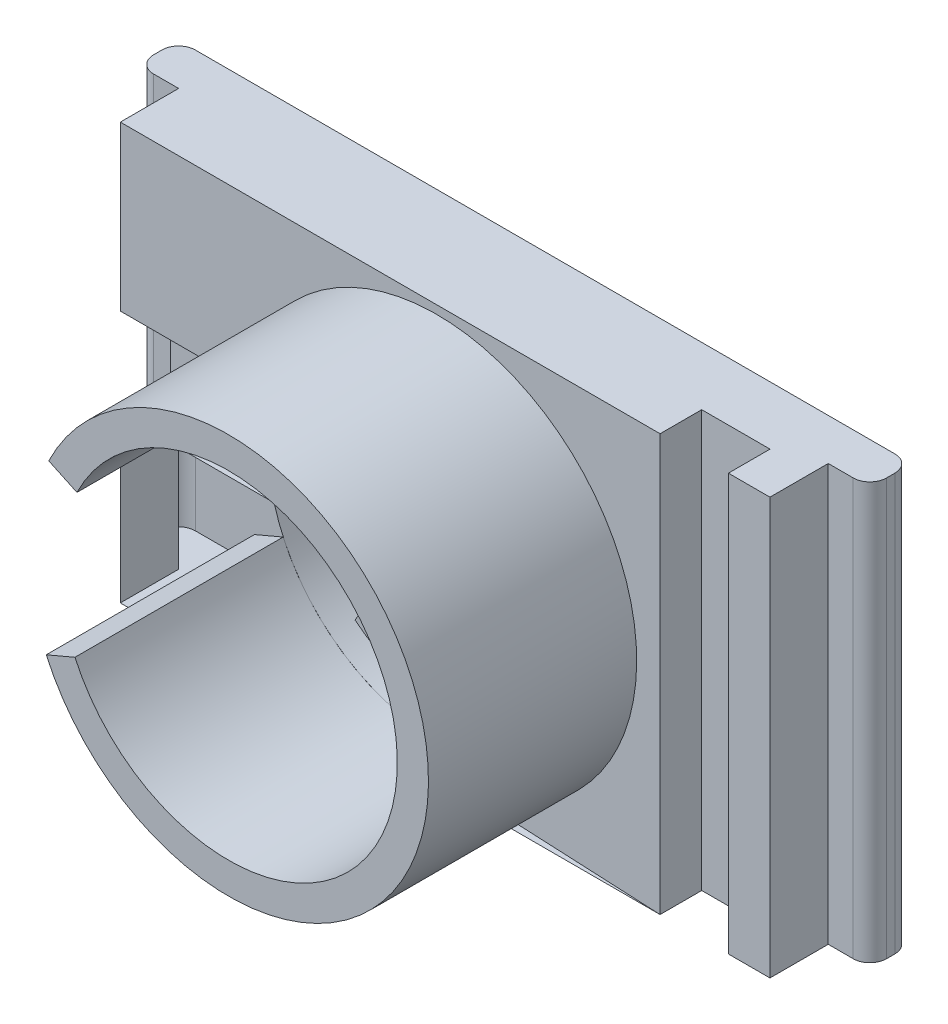
SolidWorks part; units mm, degrees
ref_plane "Front Plane" through (0, 0, 0) normal (0, 0, 1) x (1, 0, 0)
ref_plane "Top Plane" through (0, 0, 0) normal (0, 1, 0) x (1, 0, 0)
ref_plane "Right Plane" through (0, 0, 0) normal (1, 0, 0) x (0, 0, -1)
sketch "Sketch1" plane through (0, 0, 0) normal (0, 0, 1) x (1, 0, 0)
  line L1 (-32.5, -25) -> (32.5, -25)
  line L2 (-32.5, -25) -> (-32.5, 25)
  line L3 (-32.5, 25) -> (32.5, 25)
  line L4 (32.5, -25) -> (32.5, 25)
  line L5 (-32.5, -25) -> (32.5, 25) construction
  line L6 (-32.5, 25) -> (32.5, -25) construction
  point P0 (0, 0)
  dimension "D1" = 0
  dimension "D2" = 50
  dimension "D3" = 65
extrude "Boss-Extrude1" add sketch "Sketch1" along normal blind 12
sketch "Sketch2" plane through (0, 0, 12) normal (0, 0, 1) x (1, 0, 0)
  line L0 (32.5, -25) -> (32.5, 25) construction
  line L1 (-32.5, -25) -> (32.5, -25) construction
  line L2 (-1.6792, -18.9347) -> (-0.0792, -16.1634)
  line L3 (-44.0305, 5.35) -> (-14.0305, 5.35)
  line L4 (-44.0305, 5.35) -> (-44.0305, -5.35)
  line L5 (-44.0305, -5.35) -> (-14.0305, -5.35)
  line L6 (-14.0305, 5.35) -> (-14.0305, -5.35)
  line L7 (-7.3083, -15.6847) -> (-5.7083, -12.9134)
  line L8 (25.4875, 3.25) -> (22.2875, 3.25)
  line L9 (25.4875, 3.25) -> (25.4875, -3.25)
  line L10 (25.4875, -3.25) -> (22.2875, -3.25)
  line L11 (22.2875, 3.25) -> (22.2875, -3.25)
  line L12 (-0.0792, -16.1634) -> (-5.7083, -12.9134)
  line L13 (-7.3083, 15.6847) -> (-5.7083, 12.9134)
  line L14 (-1.6792, 18.9347) -> (-0.0792, 16.1634)
  line L15 (-5.7083, 12.9134) -> (-0.0792, 16.1634)
  line L16 (5.5, 0) -> (22.2875, -3.25) construction
  circle A0 centre (5.5, 0) radius 20.25
  point P25 (8, -1.4434)
  dimension "D1" = 20.25
  dimension "DK" = 40.5
  dimension "D2" = 27
  dimension "D3" = 25
  dimension "D4" = 20.25
  dimension "D5" = 30
  dimension "D6" = 10.7
  dimension "D7" = 20.25
  dimension "D8" = 20.25
  dimension "D9" = 6.5
  dimension "D10" = 3.2
  dimension "D11" = 3
  dimension "D12" = 17.0992
extrude "Cut-Extrude1" cut sketch "Sketch2" against normal blind 6 contours A0 L6 L10 L11 L8 | A0 L3 L4 L5 | L6 A0 region at (5.5839, 0, 12) region at (-14.3187, 0, 12) region at (-29.2704, 0, 12)
sketch "Sketch3" plane through (0, 0, 6) normal (0, 0, 1) x (1, 0, 0)
  circle A0 centre (5.5, 0) radius 9
  arc A1 (-1.6792, -18.9347) -> (25.4875, -3.25) centre (5.5, 0) ccw construction
  dimension "D2" = 18
  dimension "D1" = 0
extrude "Cut-Extrude2" cut sketch "Sketch3" against normal through all
sketch "Sketch4" plane through (0, 0, 12) normal (0, 0, 1) x (1, 0, 0)
  circle A0 centre (5.5, 0) radius 20.25
  arc A1 (-1.6792, -18.9347) -> (25.4875, -3.25) centre (5.5, 0) ccw construction
  dimension "D2" = 0
  dimension "D1" = 0
extrude "Cut-Extrude3" cut sketch "Sketch4" against normal blind 3
sketch "Sketch5" plane through (32.5, 0, 0) normal (1, 0, 0) x (0, 0, -1)
  line L0 (-12, -25) -> (-12, 25) construction
  line L1 (-12, -25) -> (0, -25)
  line L2 (-12, -25) -> (-12, 25)
  line L3 (-12, 25) -> (0, 25)
  line L4 (0, -25) -> (0, 25)
  line L5 (0, -25) -> (0, 25) construction
  line L6 (-12, 25) -> (0, 25) construction
  line L7 (-12, -25) -> (0, -25) construction
  dimension "D1" = 0
  dimension "D2" = 0
  dimension "D3" = 0
  dimension "D4" = 0
extrude "Boss-Extrude2" add sketch "Sketch5" along normal blind 13
sketch "Sketch6" plane through (0, 0, 12) normal (0, 0, 1) x (1, 0, 0)
  line L0 (-32.5, -25) -> (45.5, -25) construction
  line L1 (40.509, -25) -> (32.309, -25)
  line L2 (40.509, -25) -> (40.509, 25)
  line L3 (40.509, 25) -> (32.309, 25)
  line L4 (32.309, -25) -> (32.309, 25)
  line L5 (45.5, 25) -> (-32.5, 25) construction
  dimension "D1" = 0
  dimension "D2" = 8.2
  dimension "D3" = 0
extrude "Cut-Extrude4" cut sketch "Sketch6" against normal blind 5
sketch "Sketch7" plane through (45.5, 0, 0) normal (1, 0, 0) x (0, 0, -1)
  line L0 (-12, -25) -> (0, -25) construction
  line L1 (-5, -25) -> (0, -25)
  line L2 (-5, -25) -> (-5, 25)
  line L3 (-5, 25) -> (0, 25)
  line L4 (0, -25) -> (0, 25)
  line L5 (0, -25) -> (0, 25) construction
  line L6 (0, 25) -> (-12, 25) construction
  dimension "D1" = 0
  dimension "D2" = 0
  dimension "D3" = 0
  dimension "D4" = 5
extrude "Boss-Extrude3" add sketch "Sketch7" along normal blind 5
sketch "Sketch8" plane through (-32.5, 0, 0) normal (-1, 0, 0) x (0, 0, 1)
  line L0 (12, 25) -> (0, 25) construction
  line L1 (5, 25) -> (0, 25)
  line L2 (5, 25) -> (5, -25)
  line L3 (5, -25) -> (0, -25)
  line L4 (0, 25) -> (0, -25)
  line L5 (12, -25) -> (0, -25) construction
  line L6 (0, 25) -> (0, -25) construction
  dimension "D1" = 0
  dimension "D2" = 0
  dimension "D3" = 0
  dimension "D4" = 5
extrude "Boss-Extrude4" add sketch "Sketch8" along normal blind 5
fillet "Fillet1" radius 2 1 edges at (50.5, 0, 5) type face fillet first side face at (49.25, 6.25, 5) second side face at (50.5, 0, 2.5)
fillet "Fillet2" radius 2 1 edges at (-37.5, 0, 5) type face fillet first side face at (-37.5, 0, 2.5) second side face at (-36.25, -6.25, 5)
sketch "Sketch9" plane through (0, 0, 12) normal (0, 0, 1) x (1, 0, 0)
  line L0 (-12.47, 8.7795) -> (-16.093, 10.4759)
  line L1 (-12.7089, -8.2726) -> (-16.3918, -9.8362)
  circle A0 centre (5.5, 0) radius 20.26
  circle A1 centre (5.5, 0) radius 24
  arc A2 (-14.0305, -5.35) -> (-14.0305, 5.35) centre (5.5, 0) ccw construction
  dimension "D1" = 0
  dimension "D2" = 0
  dimension "D3" = 0.01
  dimension "D4" = 48
  dimension "D5" = 20
  dimension "D6" = 24
  dimension "D7" = 24
  dimension "D8" = 20
extrude "Boss-Extrude6" add sketch "Sketch9" along normal blind 25 contours L1 A1 L0 A0 region at (-14.1176, 10.2842, 12)
fillet "Fillet3" radius 2 1 edges at (-37.5, 0, 0) type face fillet first side face at (14.5, 0, 0) second side face at (-37.5, 0, 1.5)
fillet "Fillet4" radius 2 1 edges at (50.5, 0, 0) type face fillet first side face at (50.5, 0, 1.5) second side face at (14.5, 0, 0)
